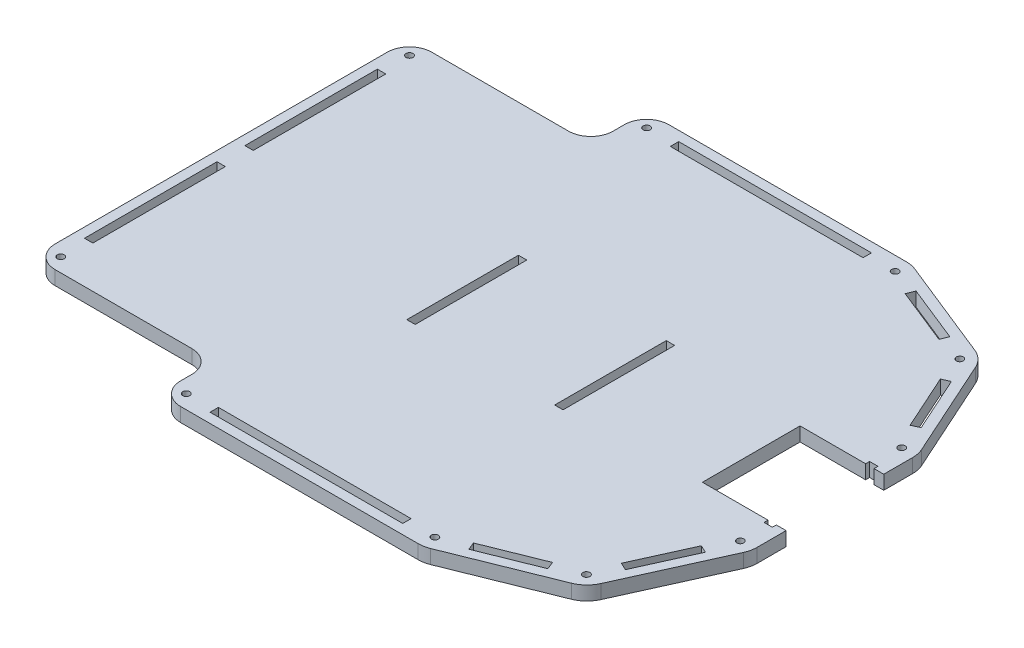
SolidWorks part; units mm, degrees
material "PVC rigido"
ref_plane "Piano frontale" through (0, 0, 0) normal (0, 0, 1) x (1, 0, 0)
ref_plane "Piano superiore" through (0, 0, 0) normal (0, 1, 0) x (1, 0, 0)
ref_plane "Piano destro" through (0, 0, 0) normal (1, 0, 0) x (0, 0, -1)
sketch "Schizzo1" plane through (0, 0, 0) normal (0, 1, 0) x (1, 0, 0)
  line L0 (65, 67.5) -> (65, 87.5)
  line L1 (0, 67.5) -> (65, 67.5)
  line L2 (0, 67.5) -> (0, -67.5)
  line L3 (0, -67.5) -> (65, -67.5)
  line L4 (65, 67.5) -> (65, -67.5) construction
  line L5 (65, 87.5) -> (160.0521, 87.5)
  line L6 (220, 30) -> (220, -30)
  line L7 (160.0521, -87.5) -> (65, -87.5)
  line L8 (65, -87.5) -> (65, -67.5)
  line L9 (220, 0) -> (65, 0) construction
  line L10 (220, 30) -> (201.5852, 70.8013)
  line L11 (201.5852, 70.8013) -> (160.0521, 87.5)
  line L12 (220, -30) -> (201.5852, -70.8013)
  line L13 (201.5852, -70.8013) -> (160.0521, -87.5)
  arc A0 (220, 30) -> (160.0521, 87.5) centre (160.0521, 27.5) ccw construction
  arc A1 (160.0521, -87.5) -> (220, -30) centre (160.0521, -27.5) ccw construction
  dimension "D5" = 60
  dimension "D6" = 60
  dimension "D1" = 135
  dimension "D2" = 65
  dimension "D3" = 155
  dimension "D4" = 20
extrude "Estrusione-Estrusione1" add sketch "Schizzo1" along normal blind 5
hole_wizard "Foro filettato M3x0.5-1" positions "Schizzo9" profile "Schizzo8" tap size "M3x0.5" standard "Ansi Metric"
sketch "Schizzo9" plane through (0, 5, 0) normal (0, 1, 0) x (1, 0, 0)
  line L102 (5, -62.5) -> (70, -62.5)
  line L103 (5, 62.5) -> (5, -62.5)
  line L104 (70, 62.5) -> (5, 62.5)
  line L105 (70, 82.5) -> (70, 62.5)
  line L106 (70, -62.5) -> (70, -82.5)
  line L107 (70, -82.5) -> (159.0846, -82.5)
  line L108 (159.0846, -82.5) -> (197.8549, -66.9121)
  line L109 (197.8549, -66.9121) -> (215, -28.9239)
  line L110 (215, -28.9239) -> (215, 28.9239)
  line L111 (215, 28.9239) -> (197.8549, 66.9121)
  line L112 (197.8549, 66.9121) -> (159.0846, 82.5)
  line L113 (159.0846, 82.5) -> (70, 82.5)
  line L114 (5, -62.5) -> (70, -62.5) construction
  line L115 (5, 62.5) -> (5, -62.5) construction
  line L116 (70, 62.5) -> (5, 62.5) construction
  line L117 (70, 82.5) -> (70, 62.5) construction
  line L118 (70, -62.5) -> (70, -82.5) construction
  line L119 (70, -82.5) -> (159.0846, -82.5) construction
  line L120 (159.0846, -82.5) -> (197.8549, -66.9121) construction
  line L121 (197.8549, -66.9121) -> (215, -28.9239) construction
  line L122 (215, -28.9239) -> (215, 28.9239) construction
  line L123 (215, 28.9239) -> (197.8549, 66.9121) construction
  line L124 (197.8549, 66.9121) -> (159.0846, 82.5) construction
  line L125 (159.0846, 82.5) -> (70, 82.5) construction
  point P0 (197.8549, 66.9121)
  point P2 (215, 28.9239)
  point P4 (215, -28.9239)
  point P6 (197.8549, -66.9121)
  point P8 (159.0846, -82.5)
  point P10 (159.0846, 82.5)
  point P12 (70, 82.5)
  point P14 (70, -82.5)
  point P16 (5, -62.5)
  point P18 (5, 62.5)
  dimension "D1" = 5
sketch "Schizzo8" plane through (197.8549, 5, -66.9121) normal (1, 0, 0) x (0, 0, 1)
  line L0 (0, 0) -> (0, 8.2511)
  line L1 (0, 8.2511) -> (1.25, 7.5)
  line L2 (1.25, 7.5) -> (1.25, 0)
  line L5 (1.25, 0) -> (0, 0)
  line L10 (0, 8.2511) -> (-1.25, 7.5) construction
  line L11 (0, -6.35) -> (0, 107.95) construction
  dimension "Tap Drill Dia." = 2.5
  dimension "Tap Drill Depth" = 7.5
  dimension "Drill Angle" = 118
cosmetic thread "Filettatura del foro1" parameters "D1"=5, "D2"=3
cosmetic thread "Filettatura del foro2" parameters "D1"=5, "D2"=3
cosmetic thread "Filettatura del foro3" parameters "D1"=5, "D2"=3
cosmetic thread "Filettatura del foro4" parameters "D1"=5, "D2"=3
cosmetic thread "Filettatura del foro5" parameters "D1"=5, "D2"=3
cosmetic thread "Filettatura del foro6" parameters "D1"=5, "D2"=3
cosmetic thread "Filettatura del foro7" parameters "D1"=5, "D2"=3
cosmetic thread "Filettatura del foro8" parameters "D1"=5, "D2"=3
cosmetic thread "Filettatura del foro9" parameters "D1"=5, "D2"=3
cosmetic thread "Filettatura del foro10" parameters "D1"=5, "D2"=3
sketch "Schizzo4" plane through (0, 5, 0) normal (0, 1, 0) x (1, 0, 0)
  line L0 (112.5261, -87.5) -> (112.5261, -84) construction
  line L1 (80, -84) -> (149.0846, -84)
  line L2 (80, -84) -> (80, -81)
  line L3 (80, -81) -> (149.0846, -81)
  line L4 (149.0846, -84) -> (149.0846, -81)
  line L5 (209.5191, 37.4216) -> (200.6014, 57.1804)
  line L6 (149.0846, -82.5) -> (159.0846, -82.5) construction
  line L7 (159.0846, -82.5) -> (168.3628, -78.7696) construction
  line L8 (168.3628, -78.7696) -> (188.5767, -70.6425) construction
  line L9 (80, 84) -> (149.0846, 84)
  line L10 (80, 84) -> (80, 81)
  line L11 (80, 81) -> (149.0846, 81)
  line L12 (149.0846, 84) -> (149.0846, 81)
  line L13 (65, -87.5) -> (160.0521, -87.5) construction
  line L14 (80, -82.5) -> (70, -82.5) construction
  line L15 (200.6014, 57.1804) -> (203.3358, 58.4145)
  line L16 (112.5261, 87.5) -> (112.5261, 84) construction
  line L17 (160.0521, 87.5) -> (65, 87.5) construction
  line L18 (80, 82.5) -> (70, 82.5) construction
  line L19 (203.3358, 58.4145) -> (212.2535, 38.6557)
  line L20 (188.5767, -70.6425) -> (197.8549, -66.9121) construction
  line L21 (197.8549, -66.9121) -> (201.9686, -57.7974) construction
  line L22 (201.9686, -57.7974) -> (210.8863, -38.0386) construction
  line L23 (210.8863, -38.0386) -> (215, -28.9239) construction
  line L24 (215, -28.9239) -> (215, -18.9239) construction
  line L25 (215, -18.9239) -> (215, 18.9239) construction
  line L26 (215, 18.9239) -> (215, 28.9239) construction
  line L27 (215, 28.9239) -> (210.8863, 38.0386) construction
  line L28 (210.8863, 38.0386) -> (201.9686, 57.7974) construction
  line L29 (201.9686, 57.7974) -> (197.8549, 66.9121) construction
  line L30 (197.8549, 66.9121) -> (188.5767, 70.6425) construction
  line L31 (188.5767, 70.6425) -> (168.3628, 78.7696) construction
  line L32 (168.3628, 78.7696) -> (159.0846, 82.5) construction
  line L33 (159.0846, 82.5) -> (149.0846, 82.5) construction
  line L34 (189.1362, 72.0342) -> (168.9223, 80.1614)
  line L35 (168.9223, 80.1614) -> (167.8032, 77.3779)
  line L36 (167.8032, 77.3779) -> (188.0171, 69.2507)
  line L37 (188.0171, 69.2507) -> (189.1362, 72.0342)
  line L38 (201.5852, 70.8013) -> (160.0521, 87.5) construction
  line L39 (212.2535, 38.6557) -> (209.5191, 37.4216)
  line L40 (167.8032, -77.3779) -> (188.0171, -69.2507)
  line L41 (188.0171, -69.2507) -> (189.1362, -72.0342)
  line L42 (189.1362, -72.0342) -> (168.9223, -80.1614)
  line L43 (168.9223, -80.1614) -> (167.8032, -77.3779)
  line L44 (200.6014, -57.1804) -> (209.5191, -37.4216)
  line L45 (209.5191, -37.4216) -> (212.2535, -38.6557)
  line L46 (212.2535, -38.6557) -> (203.3358, -58.4145)
  line L47 (203.3358, -58.4145) -> (200.6014, -57.1804)
  dimension "D1" = 10
  dimension "D2" = 3
extrude "Taglio-Estrusione2" cut sketch "Schizzo4" against normal blind 10
sketch "Schizzo7" plane through (0, 5, 0) normal (0, 1, 0) x (1, 0, 0)
  line L0 (5, -52.5) -> (5, -62.5) construction
  line L1 (3.5, 52.5) -> (6.5, 52.5)
  line L2 (3.5, 52.5) -> (3.5, 5)
  line L3 (3.5, 5) -> (6.5, 5)
  line L4 (6.5, 52.5) -> (6.5, 5)
  line L5 (6.5, -5) -> (3.5, -5)
  line L6 (6.5, -5) -> (6.5, -52.5)
  line L7 (6.5, -52.5) -> (3.5, -52.5)
  line L8 (3.5, -5) -> (3.5, -52.5)
  line L10 (5, 52.5) -> (5, 62.5) construction
  line L12 (5, -5) -> (5, 5) construction
  line L13 (5, 0) -> (0, 0) construction
  line L14 (0, 67.5) -> (0, -67.5) construction
  line L15 (80, -81) -> (80, -84) construction
  line L16 (80, -82.5) -> (70, -82.5) construction
  line L19 (3.5, -28.75) -> (0, -28.75) construction
  dimension "D2" = 10
extrude "Taglio-Estrusione5" cut sketch "Schizzo7" against normal blind 10
sketch "Schizzo12" plane through (0, 5, 0) normal (0, 1, 0) x (1, 0, 0)
  line L0 (114.5423, 81) -> (114.5423, -81) construction
  line L1 (86.5423, 20) -> (89.5423, 20)
  line L2 (86.5423, 20) -> (86.5423, -20)
  line L3 (86.5423, -20) -> (89.5423, -20)
  line L4 (89.5423, 20) -> (89.5423, -20)
  line L5 (139.5423, 20) -> (142.5423, 20)
  line L6 (139.5423, 20) -> (139.5423, -20)
  line L7 (139.5423, -20) -> (142.5423, -20)
  line L8 (142.5423, 20) -> (142.5423, -20)
  line L9 (80, 81) -> (149.0846, 81) construction
  line L10 (149.0846, -81) -> (80, -81) construction
  line L11 (89.5423, 0) -> (114.5423, 0) construction
  line L12 (114.5423, 0) -> (139.5423, 0) construction
  dimension "D1" = 40
  dimension "D2" = 3
  dimension "D3" = 50
extrude "Taglio-Estrusione8" cut sketch "Schizzo12" against normal through all
sketch "Schizzo2" plane through (0, 5, 0) normal (0, 1, 0) x (1, 0, 0)
  line L0 (220, 17.5) -> (190, 17.5)
  line L1 (220, -30) -> (220, 30) construction
  line L2 (190, 17.5) -> (190, -17.5)
  line L3 (190, -17.5) -> (220, -17.5)
  line L4 (190, 0) -> (220, 0) construction
  line L5 (220, -30) -> (220, -17.5) construction
  line L6 (220, 30) -> (220, 17.5) construction
  line L7 (220, -30) -> (220, 30) construction
  dimension "D1" = 30
  dimension "D2" = 35
extrude "Taglio-Estrusione1" cut sketch "Schizzo2" against normal through all and the other way through all
sketch "Schizzo11" plane through (0, 5, 0) normal (0, 1, 0) x (1, 0, 0)
  line L0 (220, -17.5) -> (190, -17.5) construction
  line L1 (213.5, -18.9239) -> (216.5, -18.9239)
  line L2 (213.5, -18.9239) -> (213.5, -17.5)
  line L3 (213.5, -17.5) -> (216.5, -17.5)
  line L4 (216.5, -18.9239) -> (216.5, -17.5)
  line L5 (190, 17.5) -> (220, 17.5) construction
  line L6 (213.5, 17.5) -> (216.5, 17.5)
  line L7 (213.5, 17.5) -> (213.5, 18.9239)
  line L8 (213.5, 18.9239) -> (216.5, 18.9239)
  line L9 (216.5, 17.5) -> (216.5, 18.9239)
  line L10 (212.2535, 38.6557) -> (209.5191, 37.4216) construction
  line L11 (209.5191, -37.4216) -> (212.2535, -38.6557) construction
extrude "Taglio-Estrusione7" cut sketch "Schizzo11" against normal blind 5
sketch "Schizzo10" [suppressed] plane through (0, 3, 0) normal (0, 1, 0) x (1, 0, 0)
  line L0 (219.811, 36.8884) -> (217.493, 34.984) construction
  line L1 (223.5, -18.2095) -> (226.5, -18.2095)
  line L2 (223.5, -18.2095) -> (223.5, 18.2095)
  line L3 (223.5, 18.2095) -> (226.5, 18.2095)
  line L4 (226.5, -18.2095) -> (226.5, 18.2095)
extrude "Taglio-Estrusione6" [suppressed] cut sketch "Schizzo10" against normal through all
fillet "Raccordo1" radius 8 6 edges at (0, 2.5, 67.5) (0, 2.5, -67.5) (65, 2.5, -87.5) (65, 2.5, 87.5) (65, 2.5, 67.5) (65, 2.5, -67.5)
fillet "Raccordo2" radius 10 6 edges at (160.0521, 2.5, -87.5) (201.5852, 2.5, -70.8013) (220, 2.5, -30) (220, 2.5, 30) (201.5852, 2.5, 70.8013) (160.0521, 2.5, 87.5)
